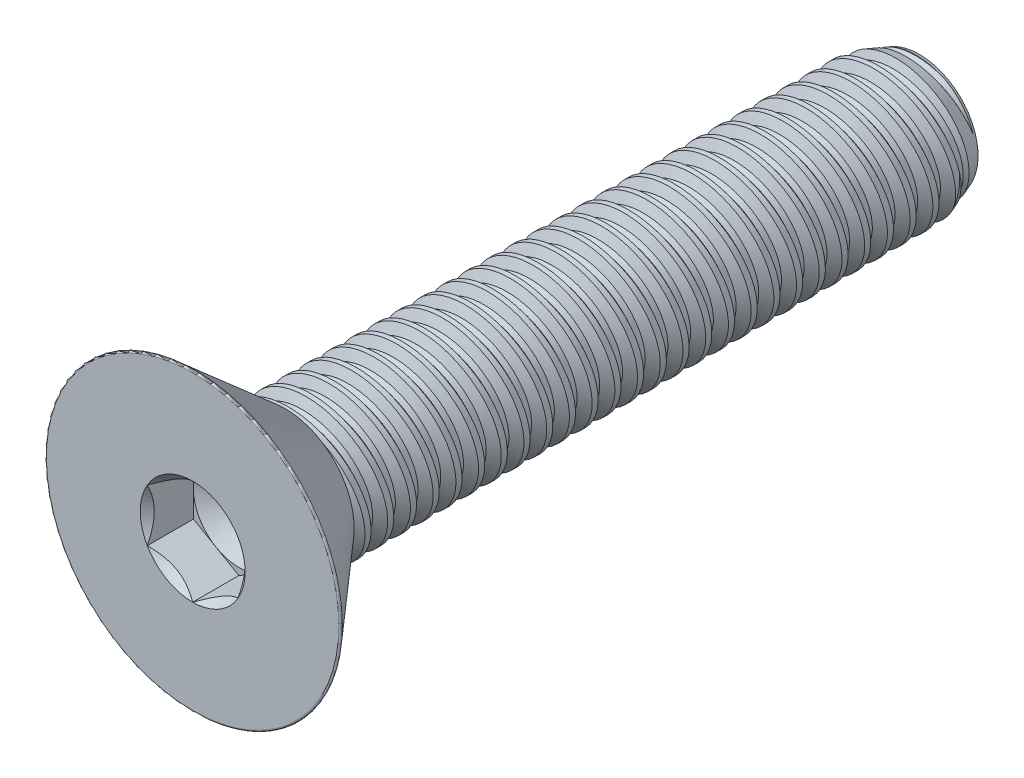
SolidWorks part; units mm, degrees
material "AISI 1045 Steel, cold drawn"
ref_plane "Front" through (0, 0, 0) normal (0, 0, 1) x (1, 0, 0)
ref_plane "Top" through (0, 0, 0) normal (0, 1, 0) x (1, 0, 0)
ref_plane "Right" through (0, 0, 0) normal (1, 0, 0) x (0, 0, -1)
sketch "Sketch1" plane through (0, 0, 0) normal (1, 0, 0) x (0, 0, -1)
  line L0 (0, 0) -> (-3.2258, 0) construction
  line L1 (0, 0) -> (22.1742, 0)
  line L2 (0, 0) -> (0, 2.413)
  line L3 (0, 2.413) -> (22.1742, 2.413)
  line L4 (22.1742, 0) -> (22.1742, 2.413)
  line L5 (0, -2.413) -> (22.1742, -2.413) construction
  dimension "D1" = 22.1742
  dimension "Thread Dia" = 4.826
  dimension "Length" = 25.4
  dimension "Head Height" = 3.2258
revolve "Revolve1" add sketch "Sketch1" angle 360 about L0
ref_plane "Plane1" through (0, 0, 3.2258) normal (0, 0, 1) x (1, 0, 0)
sketch "Sketch2" plane through (0, 0, 0) normal (1, 0, 0) x (0, 0, -1)
  line L0 (0, 2.413) -> (0, -2.413) construction
  line L1 (0, -2.413) -> (0.7938, -2.413) construction
  line L2 (0.7938, -2.413) -> (0, 2.413) construction
  line L3 (0, 2.413) -> (0.0979, 2.4291) construction
  line L4 (0.0979, 2.4291) -> (0.7832, 2.5418)
  line L5 (0.7832, 2.5418) -> (0.6082, 2.0776)
  line L6 (0.6082, 2.0776) -> (0.4124, 2.0454)
  line L7 (0.4124, 2.0454) -> (0.0979, 2.4291)
  line L8 (0.5103, 2.0615) -> (0.4406, 2.4855) construction
  line L9 (0, -2.413) -> (22.1742, -2.413) construction
  line L10 (0, 2.413) -> (22.1742, 2.413) construction
  line L12 (0.4525, 2.413) -> (1.2462, -2.413) construction
  line L13 (0, -0.1397) -> (1.6987, 0.1397) construction
  line L15 (0, 0) -> (0, 2.413) construction
  point P19 (0.8494, 0)
  dimension "D1" = 60
  dimension "Thread Pitch" = 0.7937
  dimension "D2" = 0.0992
  dimension "D3" = 0.1984
  dimension "D4" = 0.7937
revolve "Cut-Revolve1" cut sketch "Sketch2" angle 360 about L13
sketch "Sketch3" plane through (0, 0, 0) normal (1, 0, 0) x (0, 0, -1)
  line L0 (22.1742, 2.0454) -> (21.1643, 2.413)
  line L1 (21.1643, 2.413) -> (22.1742, 2.413)
  line L2 (22.1742, 2.413) -> (22.1742, 2.0454)
  line L3 (0, 2.413) -> (22.1742, 2.413) construction
  line L4 (22.1742, 0) -> (22.1742, 2.413) construction
  line L5 (21.1643, 0) -> (0, 0) construction
  line L6 (21.1643, 2.413) -> (21.1643, -2.413) construction
  line L7 (0, -2.413) -> (22.1742, -2.413) construction
  dimension "D1" = 20
  dimension "D2" = 4.826
revolve "Cut-Revolve2" cut sketch "Sketch3" angle 360 about L5
pattern_linear "LPattern1" count 28 spacing 0.7937 along (0, 0, 1)
pattern_linear "LPattern2" count 2 spacing 0.7937 along (0, 0, 1)
sketch "Sketch4" plane through (0, 0, 0) normal (0, 0, 1) x (1, 0, 0)
  circle A0 centre (0, 0) radius 5.2197
  dimension "Head Dia" = 10.4394
extrude "Extrude1" add sketch "Sketch4" along normal up to surface (3.2258 mm away)
sketch "Sketch9" plane through (0, 0, 0) normal (1, 0, 0) x (0, 0, -1)
  line L0 (-3.2258, 5.2197) -> (0, 2.4156)
  line L1 (0, 2.4156) -> (0, 5.2197)
  line L2 (0, 5.2197) -> (-3.2258, 5.2197)
  line L3 (0, 0) -> (-3.2258, 0) construction
  line L6 (-3.2258, -5.2197) -> (0, -2.4156) construction
  line L7 (0, -5.2197) -> (0, 5.2197) construction
  line L8 (-3.2258, 5.2197) -> (-3.2258, -5.2197) construction
  line L9 (0, 5.2197) -> (-3.2258, 5.2197) construction
  dimension "D1" = 82
revolve "Cut-Revolve3" cut sketch "Sketch9" angle 360 about L3
fillet "Fillet1" radius 0.0508
sketch "Sketch6" plane through (0, 0, 3.2258) normal (0, 0, 1) x (1, 0, 0)
  line L1 (0, -1.8331) -> (1.5875, -0.9165)
  line L2 (1.5875, -0.9165) -> (1.5875, 0.9165)
  line L3 (1.5875, 0.9165) -> (0, 1.8331)
  line L4 (0, 1.8331) -> (-1.5875, 0.9165)
  line L5 (-1.5875, 0.9165) -> (-1.5875, -0.9165)
  line L6 (-1.5875, -0.9165) -> (0, -1.8331)
  circle A0 centre (0, 0) radius 1.5875 construction
  dimension "Hex" = 3.175
extrude "Cut-Extrude1" cut sketch "Sketch6" against normal blind 1.6129
sketch "Sketch7" plane through (0, 0, 3.2258) normal (0, 0, 1) x (1, 0, 0)
  circle A0 centre (0, 0) radius 1.8331
extrude "Cut-Extrude4" cut sketch "Sketch7" against normal blind 1.6129 draft 45
sketch "Sketch8" plane through (0, 0, 1.6129) normal (0, 0, 1) x (1, 0, 0)
  circle A0 centre (0, 0) radius 1.5875 construction
  circle A1 centre (0, 0) radius 1.5875
extrude "Cut-Extrude5" cut sketch "Sketch8" against normal blind 0.5376 draft 60
equation "\"D2@Sketch2\"=\"Thread Pitch@Sketch2\"/8"
equation "\"D3@Sketch2\"=\"Thread Pitch@Sketch2\"/4"
equation "\"D4@Sketch2\"=\"Thread Pitch@Sketch2\""
equation "\"D3@LPattern1\"=\"Thread Pitch@Sketch2\""
equation "\"D1@Cut-Extrude1\"=\"Head Height@Sketch1\"/2"
equation "\"D1@Cut-Extrude4\"=\"D1@Cut-Extrude1\""
equation "\"D1@Cut-Extrude5\"=\"D1@Cut-Extrude1\"/3"
equation "\"D1@LPattern1\"=\"D1@Sketch1\"/\"Thread Pitch@Sketch2\""
equation "\"D3@LPattern2\"=\"Thread Pitch@Sketch2\""
